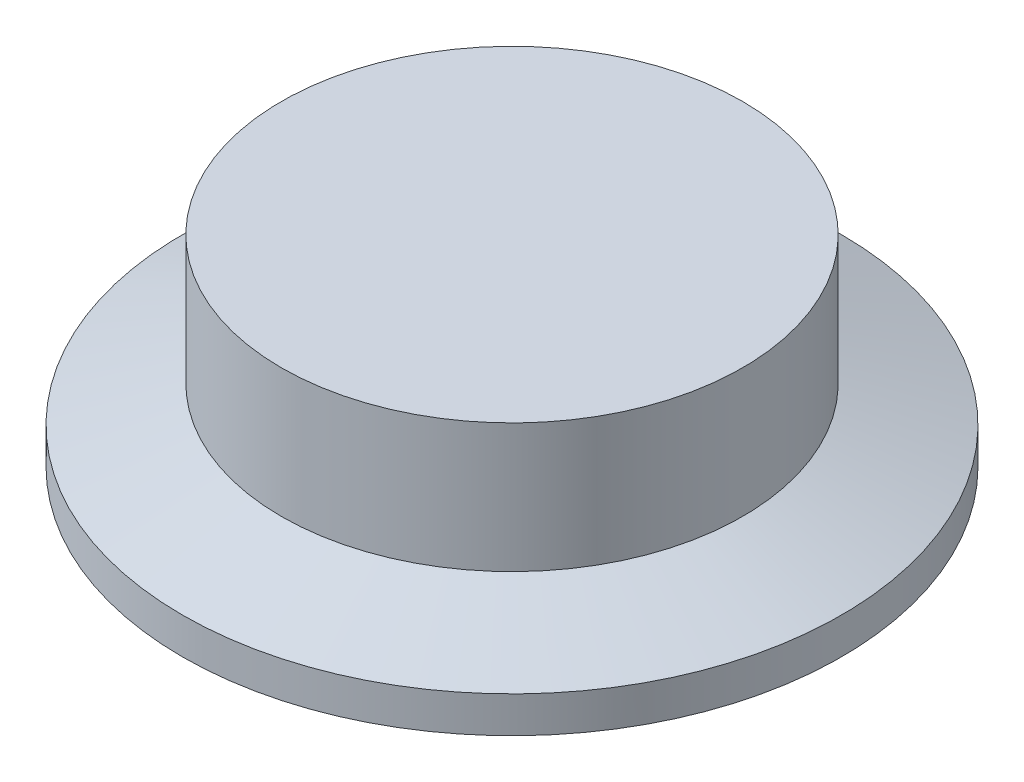
SolidWorks part; units mm, degrees
material "6061-T6 (SS)"
ref_plane "Front Plane" through (0, 0, 0) normal (0, 0, 1) x (1, 0, 0)
ref_plane "Top Plane" through (0, 0, 0) normal (0, 1, 0) x (1, 0, 0)
ref_plane "Right Plane" through (0, 0, 0) normal (1, 0, 0) x (0, 0, -1)
sketch "Sketch1" plane through (0, 0, 0) normal (0, 1, 0) x (1, 0, 0)
  circle A0 centre (0, 0) radius 93.726
  dimension "D1" = 187.452
extrude "Boss-Extrude1" add sketch "Sketch1" along normal mid plane 9.652
sketch "Sketch2" plane through (0, 0, 0) normal (0, 0, 1) x (1, 0, 0)
  line L0 (0, -18.3275) -> (0, 20.8308) construction
  line L1 (0, -4.826) -> (-25.4, -4.826)
  line L2 (-93.726, -4.826) -> (93.726, -4.826) construction
  line L3 (0, -4.826) -> (0, 1.27)
  spline S0 degree 3 poles (0, 1.27) (-5.1197, 1.5129) (-13.6852, -0.4966) (-22.1585, -2.9398) (-25.4, -4.826) knots 0 0 0 0 0.575799 1 1 1 1
  dimension "D1" = 25.4
  dimension "D2" = 6.096
revolve "Cut-Revolve1" cut sketch "Sketch2" angle 360 about L0
sketch "Sketch4" plane through (0, 4.826, 0) normal (0, 1, 0) x (1, 0, 0)
  circle A0 centre (0, 0) radius 85.09
  circle A1 centre (0, 0) radius 79.375
  dimension "D1" = 170.18
  dimension "D2" = 158.75
extrude "Boss-Extrude2" add sketch "Sketch4" along normal blind 12.7
ref_plane "Plane1" through (0, 0, -85.09) normal (0, 0, -1) x (-1, 0, 0)
sketch "Sketch5" plane through (0, 0, -85.09) normal (0, 0, -1) x (-1, 0, 0)
  line L0 (0, 19.2786) -> (0, -19.2786) construction
  line L1 (79.375, 17.526) -> (-79.375, 17.526) construction
  circle A0 centre (0, 11.176) radius 1.3525
  dimension "D1" = 2.7051
  dimension "D2" = 6.35
extrude "Cut-Extrude2" cut sketch "Sketch5" against normal blind 12.7
pattern_circular "CirPattern1" count 12 over 360 about axis through (0, 17.526, 0) along (0, -1, 0) of "Cut-Extrude2" reverse direction yes
mirror "Mirror2" about plane through (0, 0, 0) normal (0, 1, 0) of "CirPattern1", "Cut-Extrude2", "Boss-Extrude2"
sketch "Sketch6" plane through (0, 4.826, 0) normal (0, 1, 0) x (1, 0, 0)
  line L0 (-63.5, 0) -> (-69.85, 0)
  line L1 (0, -69.85) -> (0, -63.5)
  line L2 (0, -19.2786) -> (0, 19.2786) construction
  arc A0 (-69.85, 0) -> (0, -69.85) centre (0, 0) ccw
  arc A1 (-63.5, 0) -> (0, -63.5) centre (0, 0) ccw
  dimension "D1" = 69.85
  dimension "D2" = 63.5
  dimension "D3" = 90
extrude "Cut-Extrude3" [suppressed] cut sketch "Sketch6" against normal up to surface (9.652 mm away) up to face at (0, -4.826, -25.4)
sketch "Sketch7" plane through (0, 4.826, 0) normal (0, 1, 0) x (1, 0, 0)
  circle A0 centre (0, 0) radius 25.4
  circle A1 centre (0, 0) radius 127.6638
  dimension "D1" = 50.8
extrude "Cut-Extrude4" cut sketch "Sketch7" against normal through all both and the other way through all
sketch "Sketch8" plane through (0, 4.826, 0) normal (0, 1, 0) x (1, 0, 0)
  circle A0 centre (0, 0) radius 25.4
extrude "Boss-Extrude3" add sketch "Sketch8" along normal blind 5.842
sketch "Sketch9" plane through (0, 0, 0) normal (0, 0, 1) x (1, 0, 0)
  line L0 (25.4, -2.032) -> (17.78, 0.7415)
  line L1 (17.78, 0.7415) -> (17.78, 10.668)
  line L2 (17.78, 10.668) -> (25.4, 10.668)
  line L3 (25.4, 10.668) -> (25.4, -2.032)
  line L4 (25.4, 10.668) -> (-25.4, 10.668) construction
  line L5 (0, 0) -> (0, 9.2327) construction
  dimension "D1" = 17.78
  dimension "D2" = 70
  dimension "D3" = 12.7
revolve "Cut-Revolve2" cut sketch "Sketch9" angle 360 about L5
